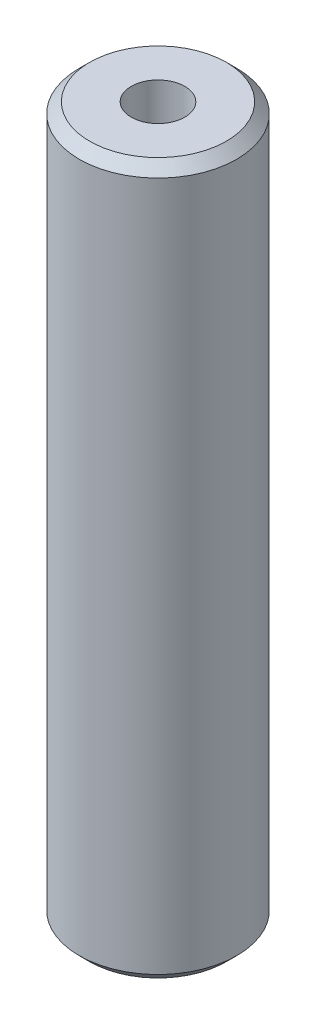
SolidWorks part; units mm, degrees
ref_plane "Front Plane" through (0, 0, 0) normal (0, 0, 1) x (1, 0, 0)
ref_plane "Top Plane" through (0, 0, 0) normal (0, 1, 0) x (1, 0, 0)
ref_plane "Right Plane" through (0, 0, 0) normal (1, 0, 0) x (0, 0, -1)
sketch "Sketch1" plane through (0, 0, 0) normal (0, 1, 0) x (1, 0, 0)
  circle A0 centre (0, 0) radius 42.5
  dimension "SHAFT_OD" = 85
extrude "Boss-Extrude1" add sketch "Sketch1" along normal blind 383.3287
sketch "Sketch2" plane through (0, 0, 0) normal (0, 1, 0) x (1, 0, 0)
  circle A0 centre (0, 0) radius 14.437
  dimension "BORE_D" = 28.8739
extrude "Cut-Extrude1" cut sketch "Sketch2" along normal through all
chamfer "Chamfer1" distance 5.6175 angle 45 2 edges at (0, 383.3287, 42.5) (0, 0, 42.5)
